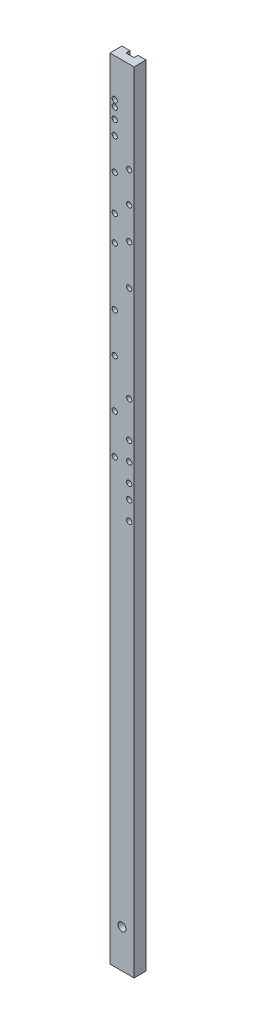
SolidWorks part; units mm, degrees
ref_plane "Front Plane" through (0, 0, 0) normal (0, 0, 1) x (1, 0, 0)
ref_plane "Top Plane" through (0, 0, 0) normal (0, 1, 0) x (1, 0, 0)
ref_plane "Right Plane" through (0, 0, 0) normal (1, 0, 0) x (0, 0, -1)
sketch "Sketch1" plane through (0, 0, 0) normal (1, 0, 0) x (0, 0, -1)
  line L1 (9.525, 622.3) -> (-9.525, 622.3)
  line L2 (9.525, 622.3) -> (9.525, -622.3)
  line L3 (9.525, -622.3) -> (-9.525, -622.3)
  line L4 (-9.525, 622.3) -> (-9.525, -622.3)
  line L5 (9.525, 622.3) -> (-9.525, -622.3) construction
  line L6 (9.525, -622.3) -> (-9.525, 622.3) construction
  point P0 (0, 0)
  dimension "D1" = 1244.6
  dimension "D2" = 19.05
extrude "Boss-Extrude1" add sketch "Sketch1" along normal mid plane 38.1
sketch "Sketch2" plane through (0, 0, 9.525) normal (0, 0, 1) x (1, 0, 0)
  line L0 (19.05, -622.3) -> (-19.05, -622.3) construction
  line L1 (0, -561.975) -> (0, -622.3) construction
  circle A0 centre (0, -561.975) radius 6.35
  dimension "D2" = 12.7
  dimension "D1" = 60.325
extrude "Cut-Extrude1" cut sketch "Sketch2" against normal through all
sketch "Sketch3" plane through (0, 0, 0) normal (1, 0, 0) x (0, 0, -1)
  line L0 (-41.275, -44.5492) -> (-50.8, -501.65)
  line L2 (-9.525, -622.3) -> (9.525, -622.3) construction
  line L3 (-52.3436, -222.1572) -> (-128.9079, -220.5617) construction
  line L4 (-44.159, -182.9492) -> (-58.8878, -182.6423)
  line L5 (-44.159, -182.9492) -> (-45.7994, -261.6721)
  line L6 (-45.7994, -261.6721) -> (-60.5282, -261.3652)
  line L7 (-58.8878, -182.6423) -> (-60.5282, -261.3652)
  line L8 (-44.159, -182.9492) -> (-60.5282, -261.3652) construction
  line L9 (-45.7994, -261.6721) -> (-58.8878, -182.6423) construction
  line L10 (-198.2402, -225.4684) -> (-59.8403, -228.3523)
  line L11 (-198.2402, -225.4684) -> (-197.9756, -212.7711)
  line L12 (-197.9756, -212.7711) -> (-59.5757, -215.6551)
  line L13 (-59.8403, -228.3523) -> (-59.5757, -215.6551)
  line L14 (-198.2402, -225.4684) -> (-59.5757, -215.6551) construction
  line L15 (-197.9756, -212.7711) -> (-59.8403, -228.3523) construction
  line L16 (-9.525, 622.3) -> (-9.525, -622.3) construction
  circle A0 centre (-46.0375, -273.0996) radius 228.6
  point P12 (-52.3436, -222.1572)
  point P13 (-128.9079, -220.5617)
  point P20 (-41.275, -501.65)
  point P21 (-41.275, -501.65)
  point P22 (-41.275, -501.65)
  point P23 (-66.8005, -501.65)
  point P24 (-65.2544, -229.6792)
  point P25 (-67.2565, -501.65)
  dimension "D1" = 457.2
  dimension "D2" = 31.75
  dimension "D3" = 120.65
  dimension "D4" = 12.7
  dimension "D5" = 138.43
  dimension "D6" = 78.74
  dimension "D7" = 14.732
  dimension "D8" = 41.275
  dimension "D9" = 177.8
ref_plane "Plane1" through (0, -223.151, 4.65) normal (0, 0.9998, -0.0208) x (0, 0.0208, 0.9998)
sketch "Sketch7" plane through (0, -223.151, 4.65) normal (0, 0.9998, -0.0208) x (0, 0.0208, 0.9998)
  line L0 (193.4999, 0) -> (55.0699, 0) construction
  line L1 (217.5832, 38.1) -> (55.0735, 38.1)
  line L2 (217.5832, 38.1) -> (217.5832, -38.1)
  line L3 (217.5832, -38.1) -> (55.0735, -38.1)
  line L4 (55.0735, 38.1) -> (55.0735, -38.1)
  line L5 (217.5832, 38.1) -> (55.0735, -38.1) construction
  line L6 (217.5832, -38.1) -> (55.0735, 38.1) construction
  point P0 (136.3283, 0)
  point P7 (55.2318, 38.1)
  point P8 (0, 0)
  point P9 (64.2735, -38.1)
  point P10 (0, 0)
  dimension "D1" = 76.2
sketch "Sketch4" plane through (0, 622.3, 0) normal (0, 1, 0) x (1, 0, 0)
  line L0 (19.05, 9.525) -> (-19.05, 9.525) construction
  line L1 (-6.35, 15.875) -> (6.35, 15.875)
  line L2 (-6.35, 15.875) -> (-6.35, 3.175)
  line L3 (-6.35, 3.175) -> (6.35, 3.175)
  line L4 (6.35, 15.875) -> (6.35, 3.175)
  line L5 (-6.35, 15.875) -> (6.35, 3.175) construction
  line L6 (-6.35, 3.175) -> (6.35, 15.875) construction
  point P0 (0, 9.525)
  dimension "D1" = 12.7
  dimension "D2" = 6.35
extrude "Cut-Extrude2" cut sketch "Sketch4" against normal through all
sketch "Sketch5" plane through (0, 0, 9.525) normal (0, 0, 1) x (1, 0, 0)
  line L0 (-11.43, 622.3) -> (-11.43, -622.3) construction
  line L1 (19.05, 622.3) -> (-19.05, 622.3) construction
  line L2 (19.05, -622.3) -> (-19.05, -622.3) construction
  line L3 (-11.43, -622.3) -> (11.43, -622.3) construction
  line L4 (11.43, -622.3) -> (11.43, 622.3) construction
  line L5 (11.43, 622.3) -> (-11.43, 622.3) construction
  line L6 (19.05, 622.3) -> (19.05, -622.3) construction
  line L7 (-19.05, 622.3) -> (-19.05, -622.3) construction
  circle A0 centre (-11.43, 513.3021) radius 1.905
  circle A1 centre (11.43, 478.2636) radius 1.905
  circle A2 centre (-11.43, 463.3456) radius 1.905
  circle A3 centre (11.43, 430.1139) radius 1.905
  circle A4 centre (-11.43, 407.0641) radius 1.905
  circle A5 centre (11.43, 379.8427) radius 1.905
  circle A6 centre (-11.43, 366.5515) radius 1.905
  circle A7 centre (11.43, 316.419) radius 1.905
  circle A8 centre (-11.43, 535.4221) radius 1.905
  circle A9 centre (-11.43, 552.285) radius 1.905
  circle A10 centre (-11.43, 562.4307) radius 1.905
  circle A11 centre (11.43, 165.1498) radius 1.905
  circle A12 centre (11.43, 108.4563) radius 1.905
  circle A13 centre (11.43, 79.0585) radius 1.905
  circle A14 centre (11.43, 49.6539) radius 1.905
  circle A15 centre (11.43, 27.0432) radius 1.905
  circle A16 centre (11.43, -2.1989) radius 1.905
  circle A17 centre (-11.43, 74.3869) radius 1.905
  circle A18 centre (-11.43, 137.0132) radius 1.905
  circle A19 centre (-11.43, 212.5967) radius 1.905
  circle A20 centre (-11.43, 275.1797) radius 1.905
  dimension "D3" = 3.81
  dimension "D1" = 7.62
  dimension "D2" = 7.62
extrude "Cut-Extrude3" cut sketch "Sketch5" against normal through all
sketch "Sketch6" plane through (0, 0, 9.525) normal (0, 0, 1) x (1, 0, 0)
  circle A0 centre (-11.43, 513.3021) radius 4.1275
  circle A1 centre (11.43, 478.2636) radius 4.1275
  circle A2 centre (-11.43, 463.3456) radius 4.1275
  circle A3 centre (11.43, 430.1139) radius 4.1275
  circle A4 centre (11.43, 379.8427) radius 4.1275
  circle A5 centre (11.43, 316.419) radius 4.1275
  circle A6 centre (-11.43, 366.5515) radius 4.1275
  circle A7 centre (-11.43, 407.0641) radius 4.1275
  circle A8 centre (-11.43, 562.4307) radius 4.1275
  circle A9 centre (-11.43, 552.285) radius 4.1275
  circle A10 centre (-11.43, 535.4221) radius 4.1275
  circle A11 centre (-11.43, 275.1797) radius 4.1275
  circle A12 centre (-11.43, 212.5967) radius 4.1275
  circle A13 centre (11.43, 165.1498) radius 4.1275
  circle A14 centre (-11.43, 137.0132) radius 4.1275
  circle A15 centre (11.43, 108.4563) radius 4.1275
  circle A16 centre (11.43, 79.0585) radius 4.1275
  circle A17 centre (-11.43, 74.3869) radius 4.1275
  circle A18 centre (11.43, 49.6539) radius 4.1275
  circle A19 centre (11.43, 27.0432) radius 4.1275
  circle A20 centre (11.43, -2.1989) radius 4.1275
  dimension "D1" = 8.255
extrude "Cut-Extrude4" cut sketch "Sketch6" against normal blind 7.747
